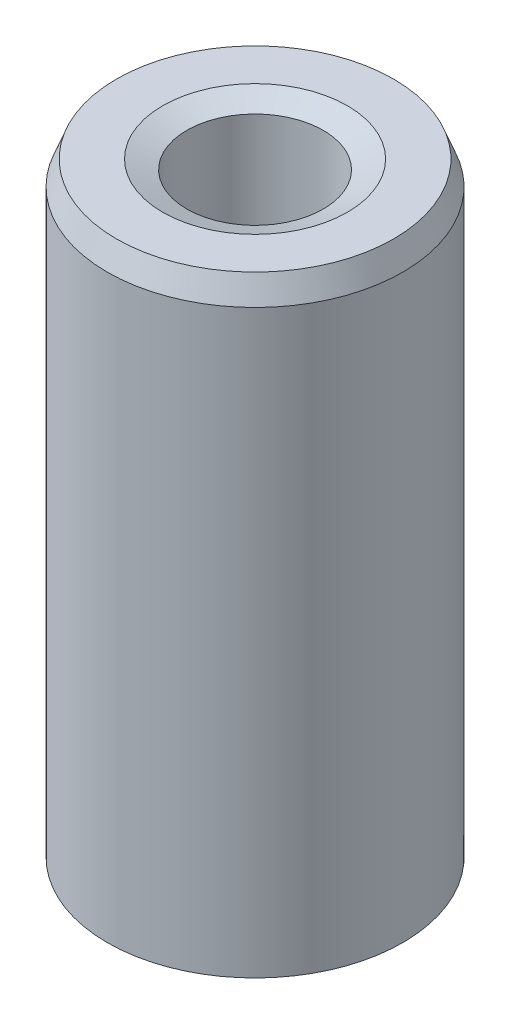
SolidWorks part; units mm, degrees
ref_plane "Front Plane" through (0, 0, 0) normal (0, 0, 1) x (1, 0, 0)
ref_plane "Top Plane" through (0, 0, 0) normal (0, 1, 0) x (1, 0, 0)
ref_plane "Right Plane" through (0, 0, 0) normal (1, 0, 0) x (0, 0, -1)
sketch "Sketch1" plane through (0, 0, 0) normal (0, 1, 0) x (1, 0, 0)
  circle A0 centre (0, 0) radius 12.5
  dimension "SLEEVE_OD" = 25
extrude "Boss-Extrude1" add sketch "Sketch1" along normal blind 51.9348
sketch "Sketch2" plane through (0, 0, 0) normal (0, 1, 0) x (1, 0, 0)
  circle A0 centre (0, 0) radius 5.7697
  dimension "BORE_D" = 11.5394
extrude "Cut-Extrude1" cut sketch "Sketch2" along normal through all
chamfer "Chamfer1" distance 2.0388 angle 21.015 4 edges at (0, 51.9348, 5.7697) (0, 0, 5.7697) (0, 0, 12.5) (0, 51.9348, 12.5) first distance on face at (0, 51.9348, 5.7697) first distance on face at (0, 0, 5.7697) first distance on face at (0, 51.9348, 12.5)
